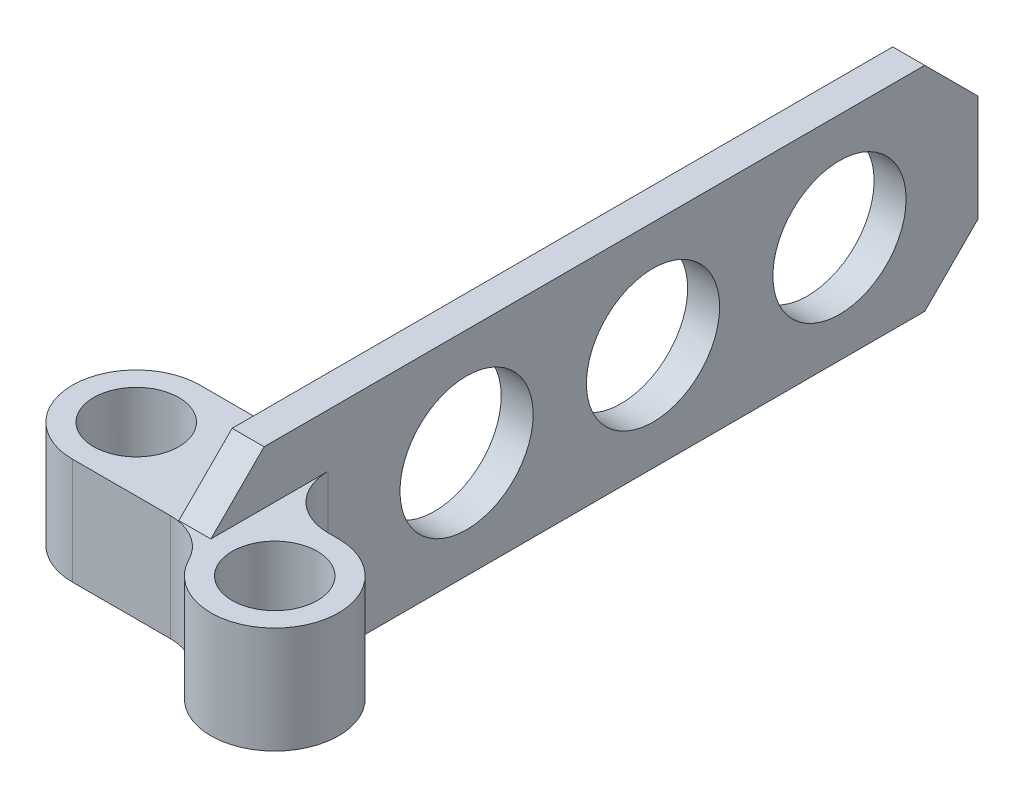
SolidWorks part; units mm, degrees
material "3003 Alloy"
ref_plane "Front Plane" through (0, 0, 0) normal (0, 0, 1) x (1, 0, 0)
ref_plane "Top Plane" through (0, 0, 0) normal (0, 1, 0) x (1, 0, 0)
ref_plane "Right Plane" through (0, 0, 0) normal (1, 0, 0) x (0, 0, -1)
sketch "Sketch1" plane through (0, 0, 0) normal (0, 1, 0) x (1, 0, 0)
  line L0 (-26, 12) -> (-26, 24) construction
  line L1 (-26, 12) -> (-38, 12) construction
  line L2 (0, 0) -> (0, 144)
  line L3 (0, 144) -> (-6, 144)
  line L4 (-6, 24) -> (-6, 144)
  line L5 (-6, 24) -> (-26, 24)
  line L7 (0, 0) -> (-26, 0)
  arc A0 (-26, 24) -> (-26, 0) centre (-26, 12) ccw
  circle A1 centre (-26, 12) radius 8
  dimension "D5" = 16
  dimension "D1" = 6
  dimension "D2" = 120
  dimension "D3" = 24
  dimension "D4" = 20
extrude "Boss-Extrude1" add sketch "Sketch1" along normal blind 40
chamfer "Chamfer1" distance 10 angle 45 2 edges at (-3, 0, -144) (-3, 40, -144)
sketch "Sketch2" plane through (0, 40, 0) normal (0, 1, 0) x (1, 0, 0)
  line L0 (-26, 12) -> (12, 12) construction
  line L1 (12, 12) -> (12, 0) construction
  line L2 (24, 0) -> (24, 24)
  line L9 (0, 24) -> (24, 24)
  line L11 (0, 0) -> (0, 134) construction
  line L12 (-6, 24) -> (-26, 24) construction
  circle A0 centre (12, 0) radius 8
  circle A1 centre (-26, 12) radius 8 construction
  arc A2 (0, 0) -> (24, 0) centre (12, 0) ccw
  arc A3 (-26, 24) -> (-26, 0) centre (-26, 12) ccw construction
  line M1 (0, 0) -> (0, 134)
extrude "Boss-Extrude2" add sketch "Sketch2" against normal through all contours A2 L2 L9 A0 M1 region at (12, 40, -9.5819)
sketch "Sketch4" plane through (0, 0, -24) normal (0, 0, -1) x (-1, 0, 0)
  line L0 (6, 20) -> (46, 20) construction
  line L1 (6, 40) -> (46, 40)
  line L2 (6, 40) -> (6, 30)
  line L3 (6, 30) -> (46, 30)
  line L4 (46, 40) -> (46, 30)
  line L5 (6, 40) -> (6, 0) construction
  line L6 (46, 20) -> (46, 30) construction
  line L7 (46, 0) -> (46, 10)
  line L8 (6, 10) -> (46, 10)
  line L9 (6, 0) -> (6, 10)
  line L10 (6, 0) -> (46, 0)
  line L11 (-40, 0) -> (-40, 10)
  line L12 (0, 40) -> (-40, 40)
  line L13 (0, 40) -> (0, 30)
  line L14 (0, 30) -> (-40, 30)
  line L15 (-40, 40) -> (-40, 30)
  line L16 (0, 10) -> (-40, 10)
  line L17 (0, 0) -> (0, 10)
  line L18 (0, 0) -> (-40, 0)
  dimension "D1" = 20
  dimension "D2" = 40
extrude "Cut-Extrude2" cut sketch "Sketch4" against normal up to next
fillet "Fillet4" radius 10 1 edges at (-6, 20, -24)
sketch "Sketch13" plane through (-6, 0, 0) normal (-1, 0, 0) x (0, 0, 1)
  line L0 (0, 30) -> (-10, 40)
  line L1 (-134, 40) -> (0, 40) construction
  line L2 (-10, 40) -> (0, 40)
  line L3 (0, 40) -> (0, 30)
  line L4 (0, 10) -> (0, 0)
  line L5 (0, 0) -> (-10, 0)
  line L6 (-134, 0) -> (0, 0) construction
  line L7 (-10, 0) -> (0, 10)
extrude "Cut-Extrude9" cut sketch "Sketch13" against normal up to next
sketch "Sketch14" plane through (0, 30, 0) normal (0, 1, 0) x (1, 0, 0)
  line L0 (12, 12) -> (0, 12)
  line L2 (0, 0) -> (0, 24) construction
  line L3 (24, 24) -> (0, 24)
  line L4 (0, 24) -> (0, 12)
  line L5 (24, 24) -> (24, 0)
  arc A0 (24, 0) -> (12, 12) centre (12, 0) ccw
  arc A1 (0, 0) -> (24, 0) centre (12, 0) ccw construction
extrude "Cut-Extrude10" cut sketch "Sketch14" against normal up to next
fillet "Fillet5" radius 10 2 edges at (0, 20, -12) (0, 20, 0)
sketch "Sketch15" plane through (0, 0, 0) normal (1, 0, 0) x (0, 0, -1)
  line L0 (144, 20) -> (22, 20) construction
  line L1 (144, 30) -> (144, 10) construction
  line L2 (22, 30) -> (22, 10) construction
  line L3 (83, 20) -> (83, 40) construction
  line L4 (10, 40) -> (134, 40) construction
  circle A0 centre (83, 20) radius 12.5
  circle A1 centre (118, 20) radius 12.5
  circle A2 centre (48, 20) radius 12.5
  dimension "D1" = 25
  dimension "D2" = 35
extrude "Cut-Extrude11" cut sketch "Sketch15" against normal up to next
